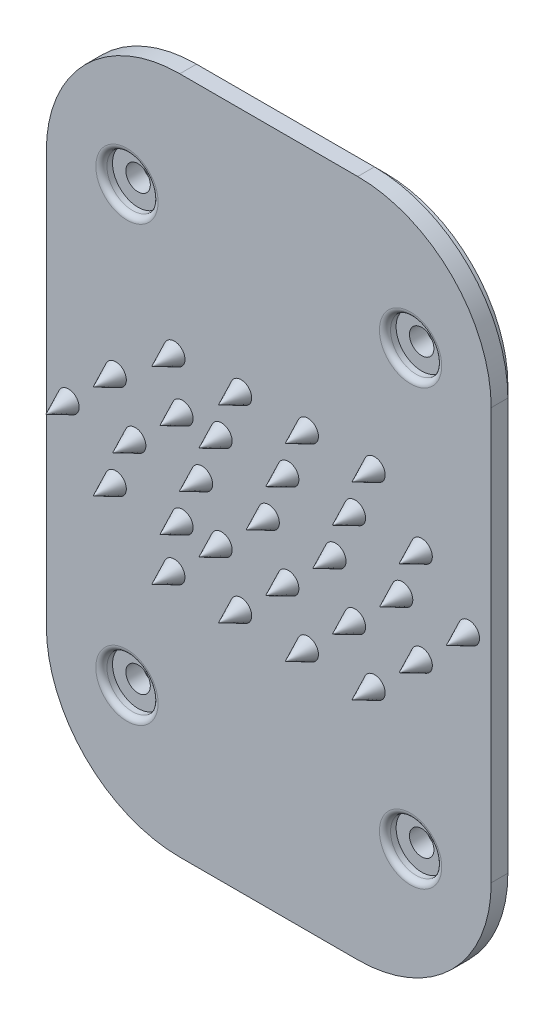
SolidWorks part; units mm, degrees
ref_plane "前视基准面" through (0, 0, 0) normal (0, 0, 1) x (1, 0, 0)
ref_plane "上视基准面" through (0, 0, 0) normal (0, 1, 0) x (1, 0, 0)
ref_plane "右视基准面" through (0, 0, 0) normal (1, 0, 0) x (0, 0, -1)
sketch "草图3" plane through (0, 0, 0) normal (0, 0, 1) x (1, 0, 0)
  line L0 (0, 28.5) -> (0, -28.5) construction
  line L2 (21, 0) -> (-21, 0) construction
  line L4 (7, 28.5) -> (-7, 28.5)
  line L5 (-18, 17.5) -> (-18, -17.5)
  line L7 (18, 17.5) -> (18, -17.5)
  line L8 (7, -28.5) -> (-7, -28.5)
  arc A0 (-7, 28.5) -> (-18, 17.5) centre (-7, 17.5) ccw
  arc A1 (7, 28.5) -> (18, 17.5) centre (7, 17.5) cw
  arc A2 (7, -28.5) -> (18, -17.5) centre (7, -17.5) ccw
  arc A3 (-7, -28.5) -> (-18, -17.5) centre (-7, -17.5) cw
  circle A4 centre (-12.75, 19.5259) radius 2.1
  circle A5 centre (12.75, 19.5259) radius 2.1
  circle A6 centre (12.75, -19.5) radius 2.1
  circle A7 centre (-12.75, -19.5) radius 2.1
  point P20 (-18, 0)
  point P22 (0, 0)
  point P28 (18, 0)
extrude "凸台-拉伸1" add sketch "草图3" along normal blind 1
sketch "草图5" plane through (0, 0, 1) normal (0, 0, 1) x (1, 0, 0)
  line L0 (0, 30.5) -> (0, -30.5) construction
  line L1 (19, 17.5) -> (19, -17.5)
  line L2 (8, 30.5) -> (-8, 30.5) construction
  line L3 (21, 0) -> (-21, 0) construction
  line L4 (-21, 19.5) -> (-21, -19.5) construction
  line L5 (-7, 29.5) -> (7, 29.5)
  line L6 (7, 29.5) -> (-7, 29.5) construction
  line L7 (-19, 17.5) -> (-19, -17.5)
  line L8 (-19, 17.5) -> (-19, -17.5) construction
  line L9 (-7, -29.5) -> (7, -29.5)
  arc A0 (-7, 29.5) -> (-19, 17.5) centre (-7, 17.5) ccw
  arc A1 (7, 29.5) -> (19, 17.5) centre (7, 17.5) cw
  arc A2 (7, -29.5) -> (19, -17.5) centre (7, -17.5) ccw
  arc A3 (-7, -29.5) -> (-19, -17.5) centre (-7, -17.5) cw
  circle A4 centre (-12.75, 19.5259) radius 1.1
  circle A5 centre (12.75, 19.5259) radius 1.1
  circle A6 centre (12.75, -19.5) radius 1.1
  circle A7 centre (-12.75, -19.5) radius 1.1
  point P17 (19, 0)
  point P23 (0, -29.5)
  point P24 (0, 29.5)
  point P25 (0, 0)
  point P31 (-19, 0)
extrude "凸台-拉伸3" add sketch "草图5" along normal blind 1
sketch "草图7" plane through (0, 0, 2) normal (0, 0, 1) x (1, 0, 0)
  line L0 (-8, 30.5) -> (8, 30.5)
  line L1 (8, 30.5) -> (-8, 30.5) construction
  line L2 (-20, 18.5) -> (-20, -18.5)
  line L3 (-20, 18.5) -> (-20, -18.5) construction
  line L4 (0, 30.5) -> (0, -30.5) construction
  line L5 (20, 0) -> (-20, 0) construction
  line L6 (20, 18.5) -> (20, -18.5)
  line L7 (-8, -30.5) -> (8, -30.5)
  arc A0 (-8, 30.5) -> (-20, 18.5) centre (-8, 18.5) ccw
  arc A1 (8, 30.5) -> (20, 18.5) centre (8, 18.5) cw
  arc A2 (8, -30.5) -> (20, -18.5) centre (8, -18.5) ccw
  arc A3 (-8, -30.5) -> (-20, -18.5) centre (-8, -18.5) cw
  circle A4 centre (-12.75, 19.5259) radius 1.1
  circle A5 centre (12.75, 19.5259) radius 1.1
  circle A6 centre (12.75, -19.5) radius 1.1
  circle A7 centre (-12.75, -19.5) radius 1.1
  point P19 (0, 0)
extrude "凸台-拉伸4" add sketch "草图7" along normal blind 1.5
sketch "草图8" plane through (0, 0, 3.5) normal (0, 0, 1) x (1, 0, 0)
  line L0 (0, -32.175) -> (0, 32.175) construction
  line L1 (27.5, 0) -> (-27.5, 0) construction
  circle A0 centre (0, 0) radius 0.9512
  circle A1 centre (6, 0) radius 0.9512
  circle A2 centre (12, 0) radius 0.9512
  circle A3 centre (18, 0) radius 0.9512
  circle A4 centre (1.7574, 4.2426) radius 0.9512
  circle A5 centre (7.7574, 4.2426) radius 0.9512
  circle A6 centre (13.7574, 4.2426) radius 0.9512
  circle A7 centre (-2.4853, 8.4853) radius 0.9512
  circle A8 centre (3.5147, 8.4853) radius 0.9512
  circle A9 centre (9.5147, 8.4853) radius 0.9512
  circle A10 centre (-4.2426, 4.2426) radius 0.9512
  circle A11 centre (-8.4853, 8.4853) radius 0.9512
  circle A12 centre (-8.4853, -8.4853) radius 0.9512
  circle A13 centre (-4.2426, -4.2426) radius 0.9512
  circle A14 centre (9.5147, -8.4853) radius 0.9512
  circle A15 centre (3.5147, -8.4853) radius 0.9512
  circle A16 centre (-2.4853, -8.4853) radius 0.9512
  circle A17 centre (13.7574, -4.2426) radius 0.9512
  circle A18 centre (7.7574, -4.2426) radius 0.9512
  circle A19 centre (1.7574, -4.2426) radius 0.9512
  circle A20 centre (-7.7574, -4.2426) radius 0.9512
  circle A21 centre (-7.7574, 4.2426) radius 0.9512
  circle A22 centre (-6, 0) radius 0.9512
  circle A23 centre (-13.7574, -4.2426) radius 0.9512
  circle A24 centre (-13.7574, 4.2426) radius 0.9512
  circle A25 centre (-18, 0) radius 0.9512
  circle A26 centre (-12, 0) radius 0.9512
  dimension "D1" = 4
  dimension "D2" = 3
extrude "凸台-拉伸5" add sketch "草图8" along normal blind 2
chamfer "倒角2" distance 2 angle 25 27 edges at (8.5636, -8.4853, 5.5) (2.5636, -8.4853, 5.5) (0.8062, -4.2426, 5.5) (6.8062, -4.2426, 5.5) (12.8062, -4.2426, 5.5) (18.9512, 0, 5.5) (12.9512, 0, 5.5) (6.9512, 0, 5.5) (0.9512, 0, 5.5) (-18.9512, 0, 5.5) (-12.8062, -4.2426, 5.5) (-3.4364, -8.4853, 5.5) (-9.4364, -8.4853, 5.5) (-6.8062, -4.2426, 5.5) (-5.1938, -4.2426, 5.5) (-6.9512, 0, 5.5) (-12.9512, 0, 5.5) (-14.7085, 4.2426, 5.5) (-8.7085, 4.2426, 5.5) (-3.2915, 4.2426, 5.5) (2.7085, 4.2426, 5.5) (8.7085, 4.2426, 5.5) (14.7085, 4.2426, 5.5) (10.4659, 8.4853, 5.5) (4.4659, 8.4853, 5.5) (-1.5341, 8.4853, 5.5) (-7.5341, 8.4853, 5.5) first distance on face at (8.5636, -8.4853, 5.5) first distance on face at (2.5636, -8.4853, 5.5) first distance on face at (0.8062, -4.2426, 5.5) first distance on face at (6.8062, -4.2426, 5.5) first distance on face at (12.8062, -4.2426, 5.5) first distance on face at (18.9512, 0, 5.5) first distance on face at (12.9512, 0, 5.5) first distance on face at (6.9512, 0, 5.5) first distance on face at (0.9512, 0, 5.5) first distance on face at (-18.9512, 0, 5.5) first distance on face at (-12.8062, -4.2426, 5.5) first distance on face at (-3.4364, -8.4853, 5.5) first distance on face at (-9.4364, -8.4853, 5.5) first distance on face at (-6.8062, -4.2426, 5.5) first distance on face at (-5.1938, -4.2426, 5.5) first distance on face at (-6.9512, 0, 5.5) first distance on face at (-12.9512, 0, 5.5) first distance on face at (-14.7085, 4.2426, 5.5) first distance on face at (-8.7085, 4.2426, 5.5) first distance on face at (-3.2915, 4.2426, 5.5) first distance on face at (2.7085, 4.2426, 5.5) first distance on face at (8.7085, 4.2426, 5.5) first distance on face at (14.7085, 4.2426, 5.5) first distance on face at (10.4659, 8.4853, 5.5) first distance on face at (4.4659, 8.4853, 5.5) first distance on face at (-1.5341, 8.4853, 5.5) first distance on face at (-7.5341, 8.4853, 5.5)
sketch "草图9" plane through (0, 0, 3.5) normal (0, 0, 1) x (1, 0, 0)
  circle A0 centre (-12.75, 19.5259) radius 2.3
  circle A1 centre (12.75, 19.5259) radius 2.3
  circle A2 centre (12.75, -19.5) radius 2.3
  circle A3 centre (-12.75, -19.5) radius 2.3
  dimension "D1" = 4.6
extrude "切除-拉伸1" cut sketch "草图9" against normal blind 1
fillet "圆角1" radius 0.5 4 edges at (-10.45, -19.5, 3.5) (15.05, -19.5, 3.5) (15.05, 19.5259, 3.5) (-10.45, 19.5259, 3.5)
